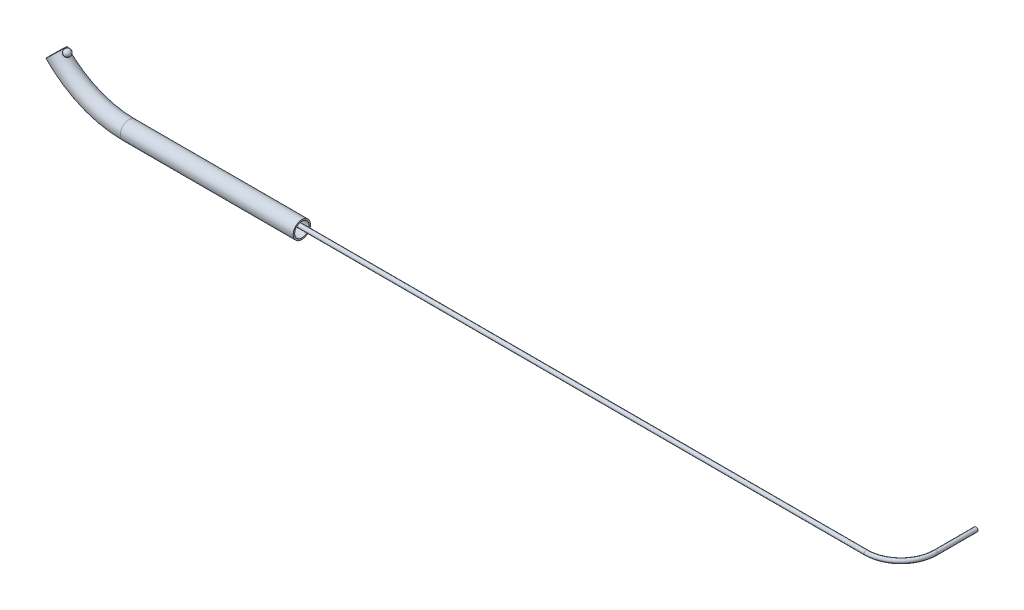
SolidWorks part; units mm, degrees
ref_plane "Front Plane" through (0, 0, 0) normal (0, 0, 1) x (1, 0, 0)
ref_plane "Top Plane" through (0, 0, 0) normal (0, 1, 0) x (1, 0, 0)
ref_plane "Right Plane" through (0, 0, 0) normal (1, 0, 0) x (0, 0, -1)
ref_axis "Axis1" through (-88.99, 0, 0) along (1, 0, 0)
sketch "Sketch4" plane through (0, 0, 0) normal (0, 0, 1) x (1, 0, 0)
  line L0 (-218.053, 283.5718) -> (61.923, 683.419) construction
  line L1 (-68.365, 0) -> (-65.9542, 0)
  arc A0 (-68.365, 0) -> (-73.5499, 2.2253) centre (-68.365, 7.1532) cw
  point P2 (-73.5499, 2.2253)
  point P3 (-68.365, 0)
sketch "Sketch1" plane through (0, 0, 0) normal (1, 0, 0) x (0, 0, -1)
  circle A0 centre (0, 0) radius 0.61
  circle A1 centre (0, 0) radius 0.39
  dimension "D1" = 1.22
  dimension "D2" = 0.22
extrude "Boss-Extrude1" [suppressed] add sketch "Sketch1" along normal blind 10
ref_plane "Plane1" through (-65.9542, 0, 0) normal (1, 0, 0) x (0, 0, -1)
sketch "Sketch5" plane through (-65.9542, 0, 0) normal (1, 0, 0) x (0, 0, -1)
  circle A0 centre (0, 0) radius 0.6223
  circle A1 centre (0, 0) radius 0.5143
  dimension "D1" = 1.2446
  dimension "D2" = 1.0287
sweep "Sweep2" add profiles "Sketch5" path "Sketch4"
extrude "Boss-Extrude2" add sketch "Sketch5<2>" along normal blind 10
sketch "Sketch5<2>" plane through (-65.9542, 0, 0) normal (1, 0, 0) x (0, 0, -1) same geometry as "Sketch5"
sketch "Sketch6" plane through (0, 0, 0) normal (0, 0, 1) x (1, 0, 0)
  line L0 (-72.7874, 2.8286) -> (-72.7874, 2.3286) construction
  line L1 (-72.9491, 2.3879) -> (-72.6257, 2.7693)
  circle A0 centre (-72.7874, 2.5786) radius 0.25 construction
  arc A1 (-72.9491, 2.3879) -> (-72.6257, 2.7693) centre (-72.7874, 2.5786) ccw
  dimension "D1" = 0.5
revolve "Revolve2" add sketch "Sketch6" angle 360 about L1
sketch "Sketch7" plane through (0, 0, 0) normal (0, 0, 1) x (1, 0, 0)
  line L0 (-68.365, -0.6223) -> (-55.9542, -0.6223) construction
  line L1 (-68.365, -0.6223) -> (-55.9542, -0.6223) construction
  line L2 (-68.365, 0.1777) -> (-55.9542, 0.1777)
  arc A1 (-74.001, 1.7966) -> (-68.365, -0.6223) centre (-68.365, 7.1532) ccw construction
  arc A2 (-74.001, 1.7966) -> (-68.365, -0.6223) centre (-68.365, 7.1532) ccw construction
  arc A3 (-73.4211, 2.3477) -> (-68.365, 0.1777) centre (-68.365, 7.1532) ccw
  dimension "D1" = 0.8
sketch "Sketch8" plane through (-36.0182, 37.8966, 0) normal (-0.6889, 0.7248, 0) x (0.7248, 0.6889, 0)
  circle A0 centre (-51.6014, 0) radius 0.15
  point P0 (-51.6014, 0)
  dimension "D1" = 0.3
sweep "Sweep3" add profiles "Sketch8" path "Sketch7"
sketch "Sketch9" plane through (-55.9542, 0, 0) normal (1, 0, 0) x (0, 0, -1)
  circle A0 centre (0, 0.1777) radius 0.15 construction
  circle A1 centre (0, 0.1777) radius 0.15
extrude "Boss-Extrude3" add sketch "Sketch9" along normal blind 40
sketch "Sketch12" plane through (-15.9542, 0, 0) normal (1, 0, 0) x (0, 0, -1)
  line L0 (0.15, 0.1777) -> (-0.15, 0.1777)
  circle A0 centre (0, 0.1777) radius 0.15 construction
ref_plane "Plane2" through (0, 0.1777, 0) normal (0, 1, 0) x (0, 0, 1)
sketch "Sketch11" plane through (-15.9542, 0, 0) normal (1, 0, 0) x (0, 0, -1)
  circle A0 centre (0, 0.1777) radius 0.15 construction
  circle A1 centre (0, 0.1777) radius 0.15
sketch "Sketch10" plane through (-32.5249, 0.1777, -2.7436) normal (0, -1, 0) x (1, 0, 0)
  line L1 (16.5707, 2.7436) -> (17.0707, 2.7436)
  line L2 (16.5707, 2.007) -> (16.5707, 3.4802) construction
  line L3 (19.5707, 0.2436) -> (19.5707, -2.6379)
  arc A0 (19.5707, 0.2436) -> (17.0707, 2.7436) centre (17.0707, 0.2436) ccw
  point P6 (19.5707, 2.7436)
  dimension "D1" = 3
  dimension "D2" = 2.5
sweep "Sweep4" add profiles "Sketch11" path "Sketch10"
